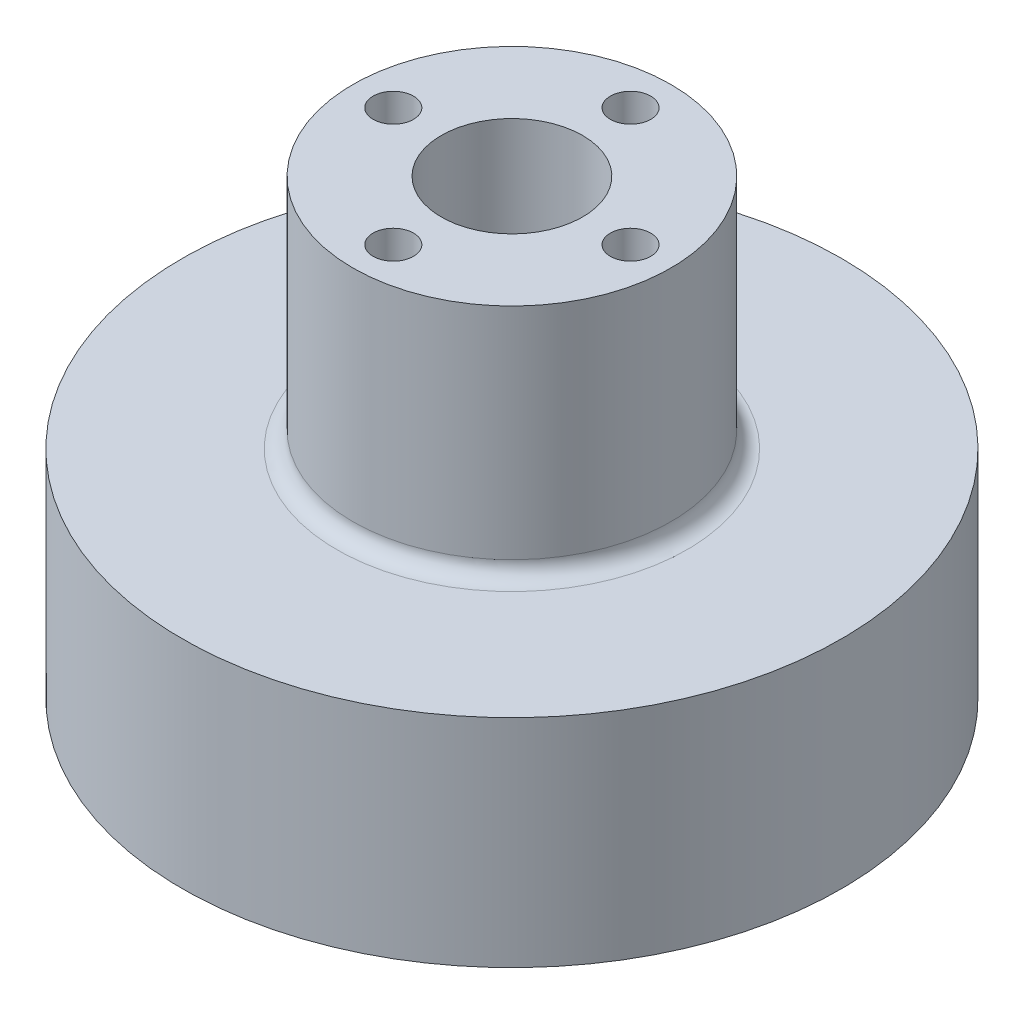
SolidWorks part; units mm, degrees
material "6061-T6 (SS)"
ref_plane "Front Plane" through (0, 0, 0) normal (0, 0, 1) x (1, 0, 0)
ref_plane "Top Plane" through (0, 0, 0) normal (0, 1, 0) x (1, 0, 0)
ref_plane "Right Plane" through (0, 0, 0) normal (1, 0, 0) x (0, 0, -1)
sketch "Sketch1" plane through (0, 0, 0) normal (1, 0, 0) x (0, 0, -1)
  line L0 (0, 0) -> (0, 17.018)
  line L1 (0, 17.018) -> (12.138, 17.018)
  line L2 (13.408, 18.288) -> (13.408, 35.56)
  line L4 (1.0795, 13.843) -> (20.3518, 13.843)
  line L5 (20.3518, 13.843) -> (20.3518, 20.447)
  line L6 (0, 0) -> (1.0795, 0)
  line L7 (13.408, 35.56) -> (20.3518, 35.56)
  line L8 (22.6441, 20.447) -> (22.6441, 26.67)
  line L9 (20.3518, 20.447) -> (22.6441, 20.447)
  line L10 (25.908, 0) -> (25.908, 53.1) construction
  line L11 (20.3518, 35.56) -> (20.3518, 26.67)
  line L12 (20.3518, 26.67) -> (22.6441, 26.67)
  line L13 (5.6426, 0) -> (5.6426, 53.1) construction
  line L14 (1.0795, 0) -> (1.0795, 53.1) construction
  line L15 (5.3264, 0) -> (5.3264, 53.1) construction
  line L16 (2.6187, 0) -> (2.6187, 53.1) construction
  line L17 (1.0795, 0) -> (1.0795, 13.843)
  arc A0 (13.408, 18.288) -> (12.138, 17.018) centre (12.138, 18.288) cw
  point P17 (13.408, 17.018)
  dimension "D11" = 1.27
  dimension "D1" = 17.018
  dimension "D2" = 3.175
  dimension "D3" = 18.542
  dimension "D4" = 6.5278
  dimension "D5" = 12.5
  dimension "D6" = 5.5562
  dimension "D8" = 25.908
  dimension "D9" = 6.604
  dimension "D10" = 8.89
  dimension "D12" = 20.2654
  dimension "D13" = 24.8285
  dimension "D14" = 4.2469
  dimension "D15" = 1.5392
revolve "Revolve1" add sketch "Sketch1" angle 360 about L10
hole_wizard "1/8 (0.125) Diameter Hole1" positions "Sketch3" profile "Sketch4" hole size "1/8" standard "ANSI Inch"
sketch "Sketch3" plane through (0, 35.56, 0) normal (0, 1, 0) x (1, 0, 0)
  circle A0 centre (0, 25.908) radius 9.325 construction
  circle A2 centre (0, 25.908) radius 12.5 construction
  point P0 (9.325, 25.908)
  point P39 (0, 16.583)
  point P40 (-9.325, 25.908)
  point P41 (0, 35.233)
  dimension "D1" = 3.175
  dimension "D2" = 4
sketch "Sketch4" plane through (9.325, 35.56, -25.908) normal (1, 0, 0) x (0, 0, 1)
  line L0 (0, 0) -> (0, 8.0976)
  line L1 (0, 8.0976) -> (1.5875, 7.1437)
  line L2 (1.5875, 7.1437) -> (1.5875, 0)
  line L5 (1.5875, 0) -> (0, 0)
  line L10 (0, 8.0976) -> (-1.5875, 7.1437) construction
  line L11 (0, -6.35) -> (0, 107.95) construction
  dimension "Hole Dia." = 3.175
  dimension "Hole Depth" = 7.1437
  dimension "Drill Angle" = 118
